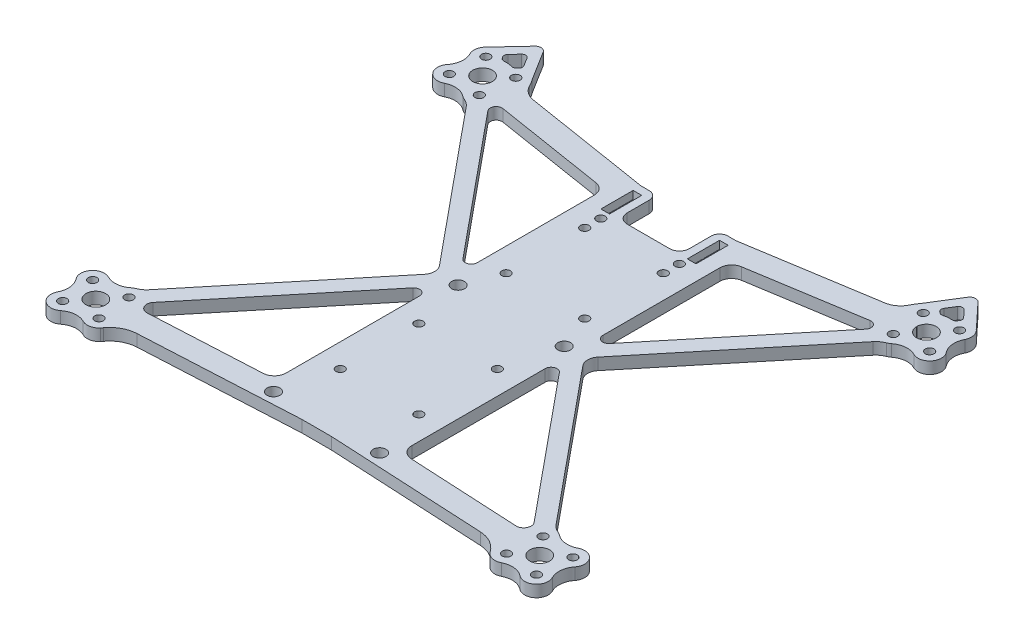
SolidWorks part; units mm, degrees
ref_plane "Front Plane" through (0, 0, 0) normal (0, 0, 1) x (1, 0, 0)
ref_plane "Top Plane" through (0, 0, 0) normal (0, 1, 0) x (1, 0, 0)
ref_plane "Right Plane" through (0, 0, 0) normal (1, 0, 0) x (0, 0, -1)
sketch "Sketch1" plane through (0, 0, 0) normal (0, 1, 0) x (1, 0, 0)
  line L0 (0, 42.225) -> (0, -42.225) construction
  line L1 (16, 42.225) -> (-16, 42.225)
  line L2 (16, 42.225) -> (16, -42.225)
  line L3 (16, -42.225) -> (-16, -42.225)
  line L4 (-16, 42.225) -> (-16, -42.225)
  line L5 (16, 42.225) -> (-16, -42.225) construction
  line L6 (16, -42.225) -> (-16, 42.225) construction
  line L12 (-12.1, 50.425) -> (-12.1, 52.425) construction
  line L17 (-11, 52.425) -> (-11, 42.225) construction
  line L18 (-7.9, 42.225) -> (-14.1, 42.225)
  line L20 (-10, 36) -> (10, 36)
  line L21 (-10, 36) -> (-10, 16)
  line L22 (-10, 16) -> (10, 16)
  line L23 (10, 36) -> (10, 16)
  line L24 (-10, 36) -> (10, 16) construction
  line L25 (-10, 16) -> (10, 36) construction
  line L26 (-14.5, 10.775) -> (14.5, 10.775)
  line L27 (-14.5, 10.775) -> (-14.5, 41.225)
  line L28 (-14.5, 41.225) -> (14.5, 41.225)
  line L29 (14.5, 10.775) -> (14.5, 41.225)
  line L30 (-14.5, 10.775) -> (14.5, 41.225) construction
  line L31 (-14.5, 41.225) -> (14.5, 10.775) construction
  line L32 (-10, -6.225) -> (10, -6.225)
  line L33 (-10, -6.225) -> (-10, -26.225)
  line L34 (-10, -26.225) -> (10, -26.225)
  line L35 (10, -6.225) -> (10, -26.225)
  line L36 (-10, -6.225) -> (10, -26.225) construction
  line L37 (-10, -26.225) -> (10, -6.225) construction
  line L38 (-15.75, -36.225) -> (15.75, -36.225)
  line L39 (-15.75, -36.225) -> (-15.75, 3.775)
  line L40 (-15.75, 3.775) -> (15.75, 3.775)
  line L41 (15.75, -36.225) -> (15.75, 3.775)
  line L42 (-15.75, -36.225) -> (15.75, 3.775) construction
  line L43 (-15.75, 3.775) -> (15.75, -36.225) construction
  line L48 (-7.9, 42.225) -> (-7.9, 52.425)
  line L49 (-7.9, 52.425) -> (-14.1, 52.425)
  line L59 (-14.1, 42.225) -> (-14.1, 52.425)
  line L63 (-12.1, 50.425) -> (-9.9, 50.425)
  line L64 (-12.1, 50.425) -> (-12.1, 42.225)
  line L65 (-12.1, 42.225) -> (-9.9, 42.225)
  line L66 (-9.9, 50.425) -> (-9.9, 42.225)
  line L67 (-12.1, 50.425) -> (-9.9, 42.225) construction
  line L68 (-12.1, 42.225) -> (-9.9, 50.425) construction
  line L69 (-12.1, 50.425) -> (-14.1, 50.425) construction
  line L74 (7.9, 42.225) -> (14.1, 42.225)
  line L75 (14.1, 42.225) -> (14.1, 52.425)
  line L76 (7.9, 52.425) -> (14.1, 52.425)
  line L77 (7.9, 42.225) -> (7.9, 52.425)
  line L78 (12.1, 50.425) -> (9.9, 50.425)
  line L79 (12.1, 50.425) -> (12.1, 42.225)
  line L80 (12.1, 42.225) -> (9.9, 42.225)
  line L81 (9.9, 50.425) -> (9.9, 42.225)
  line L82 (-14.5, 10.775) -> (-14.5, 3.775) construction
  line L83 (-14.5, 7.275) -> (16, 7.275) construction
  line L89 (-13.5, -37.225) -> (-16, -37.225) construction
  line L94 (-14.1, 52.425) -> (-16, 52.425)
  line L95 (-14.1, 52.425) -> (-14.1, 42.225)
  line L96 (-14.1, 42.225) -> (-16, 42.225)
  line L97 (-16, 52.425) -> (-16, 42.225)
  line L98 (14.1, 52.425) -> (16, 52.425)
  line L99 (14.1, 52.425) -> (14.1, 42.225)
  line L100 (14.1, 42.225) -> (16, 42.225)
  line L101 (16, 52.425) -> (16, 42.225)
  circle A3 centre (-10, 36) radius 1.1
  circle A4 centre (10, 36) radius 1.1
  circle A5 centre (10, 16) radius 1.1
  circle A6 centre (-10, 16) radius 1.1
  circle A7 centre (-10, -6.225) radius 1.1
  circle A8 centre (10, -6.225) radius 1.1
  circle A9 centre (10, -26.225) radius 1.1
  circle A10 centre (-10, -26.225) radius 1.1
  circle A37 centre (-13.5, 7.275) radius 2.5
  circle A38 centre (-13.5, 7.275) radius 1.625
  circle A39 centre (13.5, 7.275) radius 1.625
  circle A40 centre (-13.5, -39.725) radius 2.5
  circle A41 centre (-13.5, -39.725) radius 1.625
  circle A42 centre (13.5, -39.725) radius 1.625
  point P0 (0, 0)
  point P8 (0, 0)
  point P16 (0, 26)
  point P26 (0, 26)
  point P31 (0, -16.225)
  point P36 (0, -16.225)
  point P61 (-11, 46.325)
  dimension "D3" = 2
  dimension "D17" = 2.2
  dimension "D22" = 5
  dimension "D23" = 3.25
  dimension "D8" = 32
  dimension "D9" = 22
  dimension "D10" = 20
  dimension "D11" = 29
  dimension "D12" = 30.45
  dimension "D13" = 40
  dimension "D14" = 31.5
  dimension "D15" = 1
  dimension "D16" = 7
  dimension "D18" = 2.2
  dimension "D20" = 8.2
  dimension "D24" = 1
extrude "Base shape" add sketch "Sketch1" along normal blind 2 contours L63 L66 L1 L48 L49 L59 L18 L64 | L81 L78 L79 L1 L75 L76 L77 | L94 L97 L1 L59 | L101 L98 L75 L1 | L1 L4 L3 L2 | A4 | A3 | A7 | A8 | A9 | A10 | A5 | A6 | A39 | A38 | A41 | A42 region at (15.05, 0, -47.325) region at (13.1, 0, -42.3444) region at (-8.9, 0, -42.3444) region at (-15.05, 0, -47.325)
sketch "Sketch2" plane through (0, 0, 0) normal (0, -1, 0) x (1, 0, 0)
  line L0 (-12.1, -42.225) -> (-9.9, -50.425) construction
  line L1 (12.1, -42.225) -> (9.9, -50.425) construction
  line L4 (12.1, -42.225) -> (9.9, -42.225)
  line L5 (12.1, -50.425) -> (12.1, -42.225)
  line L6 (9.9, -50.425) -> (12.1, -50.425)
  line L7 (9.9, -42.225) -> (9.9, -50.425)
  line L8 (12.1, -42.225) -> (9.9, -42.225)
  line L9 (12.1, -50.425) -> (12.1, -42.225)
  line L10 (9.9, -50.425) -> (12.1, -50.425)
  line L11 (9.9, -42.225) -> (9.9, -50.425)
  line L12 (-9.9, -42.225) -> (-12.1, -42.225)
  line L13 (-9.9, -50.425) -> (-9.9, -42.225)
  line L14 (-12.1, -50.425) -> (-9.9, -50.425)
  line L15 (-12.1, -42.225) -> (-12.1, -50.425)
  line L16 (-9.9, -42.225) -> (-12.1, -42.225)
  line L17 (-9.9, -50.425) -> (-9.9, -42.225)
  line L18 (-12.1, -50.425) -> (-9.9, -50.425)
  line L19 (-12.1, -42.225) -> (-12.1, -50.425)
  circle A0 centre (-11, -46.325) radius 1.1
  circle A1 centre (11, -46.325) radius 1.1
  dimension "D1" = 0
  dimension "D2" = 0
extrude "Camera mount pockets" add sketch "Sketch2" against normal offset from surface (1 mm away) 1 contours A0 L19 | A0 L17 | A1 L9 | A1 L11 region at (11, 0, -43.8523) region at (11, 0, -48.7977) region at (-11, 0, -43.8523) region at (-11, 0, -48.7977) up to face at (11, 2, -46.325)
fillet "Main fillets" radius 2.5 6 edges at (7.9, 1, -42.225) (-7.9, 1, -42.225) (-16, 1, -52.425) (16, 1, -52.425) (-16, 1, 42.225) (16, 1, 42.225)
fillet "Inner camera mount fillets" radius 2.1 2 edges at (-7.9, 1, -52.425) (7.9, 1, -52.425)
sketch "Sketch3" plane through (0, 2, 0) normal (0, 1, 0) x (1, 0, 0)
  line L6 (12.1, 42.225) -> (12.1, 50.425)
  line L7 (9.9, 42.225) -> (12.1, 42.225)
  line L8 (-10, 52.425) -> (-13.5, 52.425)
  line L9 (-16, 49.925) -> (-16, -39.725)
  line L10 (-13.5, -42.225) -> (13.5, -42.225)
  line L11 (16, -39.725) -> (16, 49.925)
  line L12 (13.5, 52.425) -> (10, 52.425)
  line L13 (7.9, 50.325) -> (7.9, 44.725)
  line L14 (5.4, 42.225) -> (-5.4, 42.225)
  line L15 (-7.9, 44.725) -> (-7.9, 50.325)
  line L16 (-10, 52.425) -> (-13.5, 52.425)
  line L17 (-16, 49.925) -> (-16, -39.725)
  line L18 (-13.5, -42.225) -> (13.5, -42.225)
  line L19 (16, -39.725) -> (16, 49.925)
  line L20 (13.5, 52.425) -> (10, 52.425)
  line L21 (7.9, 50.325) -> (7.9, 44.725)
  line L22 (5.4, 42.225) -> (-5.4, 42.225)
  line L23 (-7.9, 44.725) -> (-7.9, 50.325)
  line L24 (9.9, 50.425) -> (9.9, 42.225)
  line L25 (12.1, 50.425) -> (9.9, 50.425)
  line L26 (12.1, 42.225) -> (12.1, 50.425)
  line L27 (9.9, 42.225) -> (12.1, 42.225)
  line L28 (9.9, 50.425) -> (9.9, 42.225)
  line L29 (12.1, 50.425) -> (9.9, 50.425)
  line L30 (-9.9, 42.225) -> (-9.9, 50.425)
  line L31 (-12.1, 42.225) -> (-9.9, 42.225)
  line L32 (-12.1, 50.425) -> (-12.1, 42.225)
  line L33 (-9.9, 50.425) -> (-12.1, 50.425)
  line L34 (-9.9, 42.225) -> (-9.9, 50.425)
  line L35 (-12.1, 42.225) -> (-9.9, 42.225)
  line L36 (-12.1, 50.425) -> (-12.1, 42.225)
  line L37 (-9.9, 50.425) -> (-12.1, 50.425)
  circle A0 centre (13.5, -39.725) radius 1.625 construction
  circle A1 centre (-13.5, -39.725) radius 1.625 construction
  circle A2 centre (-13.5, 7.275) radius 1.625 construction
  circle A3 centre (-10, -6.225) radius 1.1 construction
  circle A4 centre (-10, -26.225) radius 1.1 construction
  circle A5 centre (10, -26.225) radius 1.1 construction
  circle A6 centre (10, -6.225) radius 1.1 construction
  circle A7 centre (13.5, 7.275) radius 1.625 construction
  arc A8 (-13.5, 52.425) -> (-16, 49.925) centre (-13.5, 49.925) ccw
  arc A9 (-16, -39.725) -> (-13.5, -42.225) centre (-13.5, -39.725) ccw
  arc A10 (13.5, -42.225) -> (16, -39.725) centre (13.5, -39.725) ccw
  arc A11 (16, 49.925) -> (13.5, 52.425) centre (13.5, 49.925) ccw
  arc A12 (-7.9, 50.325) -> (-10, 52.425) centre (-10, 50.325) ccw
  arc A13 (5.4, 42.225) -> (7.9, 44.725) centre (5.4, 44.725) ccw
  arc A14 (-7.9, 44.725) -> (-5.4, 42.225) centre (-5.4, 44.725) ccw
  arc A15 (-7.9, 50.325) -> (-10, 52.425) centre (-10, 50.325) ccw
  arc A16 (-13.5, 52.425) -> (-16, 49.925) centre (-13.5, 49.925) ccw
  arc A17 (-16, -39.725) -> (-13.5, -42.225) centre (-13.5, -39.725) ccw
  arc A18 (13.5, -42.225) -> (16, -39.725) centre (13.5, -39.725) ccw
  arc A19 (16, 49.925) -> (13.5, 52.425) centre (13.5, 49.925) ccw
  arc A21 (5.4, 42.225) -> (7.9, 44.725) centre (5.4, 44.725) ccw
  arc A22 (-7.9, 44.725) -> (-5.4, 42.225) centre (-5.4, 44.725) ccw
  circle A24 centre (-10, 16) radius 1.1 construction
  circle A25 centre (-10, 36) radius 1.1 construction
  circle A26 centre (10, 36) radius 1.1 construction
  circle A27 centre (10, 16) radius 1.1 construction
  circle A28 centre (10, 16) radius 1.1
  circle A29 centre (10, 36) radius 1.1
  circle A30 centre (-10, 36) radius 1.1
  circle A31 centre (-10, 16) radius 1.1
  circle A32 centre (13.5, 7.275) radius 1.625
  circle A33 centre (10, -6.225) radius 1.1
  circle A34 centre (10, -26.225) radius 1.1
  circle A35 centre (-10, -26.225) radius 1.1
  circle A36 centre (-10, -6.225) radius 1.1
  circle A37 centre (13.5, -39.725) radius 1.625
  circle A38 centre (-13.5, -39.725) radius 1.625
  circle A39 centre (-13.5, 7.275) radius 1.625
  arc A48 (10, 52.425) -> (7.9, 50.325) centre (10, 50.325) ccw
  arc A49 (10, 52.425) -> (7.9, 50.325) centre (10, 50.325) ccw
  dimension "D1" = 0
  dimension "D2" = 0
  dimension "D3" = 0
extrude "Thicker base" add sketch "Sketch3" along normal blind 1
sketch "Sketch4" plane through (0, 0, 0) normal (0, -1, 0) x (1, 0, 0)
  line L0 (0, 13.9568) -> (0, -8.6953) construction
  line L1 (-13.1, -38.5) -> (-6.9, -38.5)
  line L2 (-14.1, -39.5) -> (-14.1, -40.7)
  line L3 (-13.1, -41.7) -> (-6.9, -41.7)
  line L4 (-5.9, -39.5) -> (-5.9, -40.7)
  line L5 (-10, -38.5) -> (-10, -41.7) construction
  line L7 (13.1, -38.5) -> (6.9, -38.5)
  line L8 (14.1, -39.5) -> (14.1, -40.7)
  line L9 (13.1, -41.7) -> (6.9, -41.7)
  line L10 (5.9, -39.5) -> (5.9, -40.7)
  line L12 (-14.1, -40.1) -> (-5.9, -40.1) construction
  circle A0 centre (-10, -36) radius 2
  arc A9 (14.1, -40.7) -> (13.1, -41.7) centre (13.1, -40.7) cw
  arc A10 (13.1, -38.5) -> (14.1, -39.5) centre (13.1, -39.5) cw
  arc A11 (6.9, -41.7) -> (5.9, -40.7) centre (6.9, -40.7) cw
  arc A12 (6.9, -38.5) -> (5.9, -39.5) centre (6.9, -39.5) ccw
  arc A13 (-6.9, -41.7) -> (-5.9, -40.7) centre (-6.9, -40.7) ccw
  arc A14 (-6.9, -38.5) -> (-5.9, -39.5) centre (-6.9, -39.5) cw
  arc A15 (-14.1, -40.7) -> (-13.1, -41.7) centre (-13.1, -40.7) ccw
  arc A16 (-13.1, -38.5) -> (-14.1, -39.5) centre (-13.1, -39.5) ccw
  point P9 (-10, -38)
  point P19 (14.1, -41.7)
  point P24 (14.1, -38.5)
  point P27 (5.9, -41.7)
  point P30 (5.9, -38.5)
  point P33 (-5.9, -41.7)
  point P36 (-5.9, -38.5)
  point P39 (-14.1, -41.7)
  point P42 (-14.1, -38.5)
  dimension "D5" = 4
  dimension "D6" = 1
  dimension "D1" = 8.2
  dimension "D2" = 3.2
  dimension "D3" = 10
  dimension "D4" = 0.5
extrude "Battery holder pockets" cut sketch "Sketch4" against normal blind 1 contours L4 L1 L2 L3 | L7 L10 L9 L8 region at (-10, 0, -40.1) region at (10, 0, -40.1)
sketch "Sketch5" plane through (0, 1, 0) normal (0, -1, 0) x (1, 0, 0)
  line L0 (-10, -38.5) -> (-10, -41.7) construction
  line L2 (-13.1, -41.7) -> (-6.9, -41.7) construction
  line L3 (0, 5.9884) -> (0, -5.6723) construction
  line L4 (-13.1, -38.5) -> (-6.9, -38.5) construction
  circle A0 centre (-10, -40.1) radius 1.1
  circle A1 centre (10, -40.1) radius 1.1
  point P2 (-10, -38.5)
  dimension "D1" = 2.2
extrude "Battery holder holes" cut sketch "Sketch5" against normal up to next
sketch "Sketch6" [suppressed] plane through (0, 0, 0) normal (0, -1, 0) x (1, 0, 0)
  line L0 (0, -5.1) -> (0, 9.653) construction
  line L8 (-13.5, -7.275) -> (13.5, -7.275) construction
  line L10 (-16, -25.775) -> (16, -25.775) construction
  line L11 (-16, -49.925) -> (-16, 39.725) construction
  line L12 (16, -49.925) -> (16, 39.725) construction
  line L13 (17.5, -34.275) -> (19, -34.275)
  line L14 (16, -37.275) -> (19, -37.275)
  line L15 (16, -37.275) -> (16, -14.275)
  line L16 (16, -14.275) -> (19, -14.275)
  line L17 (19, -37.275) -> (19, -14.275)
  line L18 (16, -37.275) -> (19, -14.275) construction
  line L19 (16, -14.275) -> (19, -37.275) construction
  line L20 (16, -35.775) -> (17.5, -35.775)
  line L21 (16, -35.775) -> (16, -15.775)
  line L22 (16, -15.775) -> (17.5, -15.775)
  line L23 (17.5, -35.775) -> (17.5, -15.775)
  line L24 (16, -35.775) -> (17.5, -15.775) construction
  line L25 (16, -15.775) -> (17.5, -35.775) construction
  line L26 (17.5, -17.275) -> (19, -17.275)
  line L27 (-17.5, -34.275) -> (-19, -34.275)
  line L28 (-17.5, -17.275) -> (-19, -17.275)
  line L29 (-16, -35.775) -> (-16, -15.775)
  line L30 (-16, -35.775) -> (-17.5, -35.775)
  line L31 (-17.5, -35.775) -> (-17.5, -15.775)
  line L32 (-16, -15.775) -> (-17.5, -15.775)
  line L33 (-16, -37.275) -> (-16, -14.275)
  line L34 (-16, -37.275) -> (-19, -37.275)
  line L35 (-19, -37.275) -> (-19, -14.275)
  line L36 (-16, -14.275) -> (-19, -14.275)
  line L37 (16, 22.725) -> (19, 22.725)
  line L38 (16, 22.725) -> (16, -0.275)
  line L39 (16, -0.275) -> (19, -0.275)
  line L40 (19, 22.725) -> (19, -0.275)
  line L41 (16, 21.225) -> (17.5, 21.225)
  line L42 (16, 21.225) -> (16, 1.225)
  line L43 (16, 1.225) -> (17.5, 1.225)
  line L44 (17.5, 21.225) -> (17.5, 1.225)
  line L45 (17.5, 2.725) -> (19, 2.725)
  line L46 (17.5, 19.725) -> (19, 19.725)
  line L47 (-17.5, 19.725) -> (-19, 19.725)
  line L48 (-17.5, 2.725) -> (-19, 2.725)
  line L49 (-16, 21.225) -> (-16, 1.225)
  line L50 (-16, 21.225) -> (-17.5, 21.225)
  line L51 (-17.5, 21.225) -> (-17.5, 1.225)
  line L52 (-16, 1.225) -> (-17.5, 1.225)
  line L53 (-16, 22.725) -> (-16, -0.275)
  line L54 (-16, 22.725) -> (-19, 22.725)
  line L55 (-19, 22.725) -> (-19, -0.275)
  line L56 (-16, -0.275) -> (-19, -0.275)
  point P19 (17.5, -25.775)
  point P25 (16.75, -25.775)
  line M18 (16, -49.925) -> (16, 39.725)
  line M22 (-16, 39.725) -> (-16, -49.925)
  dimension "D1" = 14
  dimension "D4" = 23
  dimension "D5" = 3
  dimension "D6" = 1.5
  dimension "D7" = 20
  dimension "D8" = 1.5
extrude "Strap holders" [suppressed] add sketch "Sketch6" against normal up to surface (2 mm away) contours L23 L20 L14 L17 L13 M18 | L23 L26 L17 L16 L22 M18 | L45 L44 L43 L39 L40 M18 | L44 L46 L40 L37 L38 L41 | L54 L55 L47 L51 L50 M22 | L56 L52 L51 L48 L55 M22 | L36 L35 L28 L31 L32 M22 | L35 L34 L30 L31 L27 M22 up to face at (-10, 3, -39)
fillet "Strap holder fillets" [suppressed] radius 0.75
sketch "Sketch7" plane through (0, 3, 0) normal (0, 1, 0) x (1, 0, 0)
  line L0 (-56.5, 56.5) -> (-16, 50.0116) construction
  line L1 (56.5, -56.5) -> (-56.5, -56.5)
  line L2 (56.5, -56.5) -> (56.5, 56.5)
  line L3 (56.5, 56.5) -> (-56.5, 56.5)
  line L4 (-56.5, -56.5) -> (-56.5, 56.5)
  line L5 (56.5, -56.5) -> (-56.5, 56.5) construction
  line L6 (56.5, 56.5) -> (-56.5, -56.5) construction
  line L7 (-16, 49.925) -> (-16, -39.725) construction
  line L8 (-56.9746, 53.5378) -> (-16.4746, 47.0493)
  line L9 (-47.647, 58.1199) -> (-12.1, 52.425)
  line L10 (-56.0254, 59.4622) -> (-15.5254, 52.9738) construction
  line L11 (-13.5, 7.275) -> (13.5, 7.275) construction
  line L12 (-63.45, 50.7819) -> (-49.55, 62.2181) construction
  line L13 (-56.5, 56.5) -> (-16, 7.275) construction
  line L14 (-58.0444, 55.2293) -> (-17.5444, 6.0043)
  line L15 (-54.9556, 57.7707) -> (-14.4556, 8.5457)
  line L16 (-17.5444, 6.0043) -> (-16, 4.1271)
  line L17 (-56.5, 56.5) -> (-60.3121, 61.1333) construction
  line L18 (-56.5, 65.5) -> (-56.5, 47.5) construction
  line L19 (-60.3121, 61.1333) -> (-51.8667, 60.3121) construction
  line L20 (-56.0894, 60.7227) -> (-55.3151, 68.6852) construction
  line L21 (-56.4116, 69.7087) -> (-62.3842, 63.31)
  line L22 (-54.0419, 69.4782) -> (-49.414, 62.0488)
  line L23 (-55.4603, 67.1922) -> (-58.7341, 63.6848)
  line L24 (-55.4603, 67.1922) -> (-52.9235, 63.1198)
  line L25 (-58.0444, -40.6793) -> (-17.5444, 8.5457)
  line L26 (-54.9556, -43.2207) -> (-14.4556, 6.0043)
  line L27 (-56.5, -41.95) -> (-13.5, -39.725) construction
  line L28 (-47.871, -44.5075) -> (-3.7595, -42.225)
  line L29 (-56.655, -38.954) -> (-16, -36.8503)
  line L30 (-56.345, -44.946) -> (-14.5762, -42.7847) construction
  line L31 (-56.5, -41.95) -> (-14.7312, -39.7887) construction
  line L32 (-13.5, -42.225) -> (13.5, -42.225) construction
  line L33 (-56.655, -38.954) -> (-14.8862, -36.7927) construction
  line L34 (-16.4746, 47.0493) -> (-16, 46.9733)
  line L35 (-12.1, 50.425) -> (-12.1, 52.425) construction
  line L36 (-10, 52.425) -> (-13.5, 52.425) construction
  circle A0 centre (-56.5, 56.5) radius 38.1
  circle A1 centre (-56.5, 56.5) radius 9
  circle A2 centre (-56.5, 56.5) radius 6
  circle A3 centre (-51.8667, 60.3121) radius 1.1
  circle A4 centre (-61.1333, 52.6879) radius 1.1
  circle A5 centre (-60.3121, 61.1333) radius 1.1
  circle A6 centre (-52.6879, 51.8667) radius 1.1
  circle A7 centre (-60.3121, 61.1333) radius 3
  circle A8 centre (-51.8667, 60.3121) radius 3
  circle A9 centre (-61.1333, 52.6879) radius 3
  circle A10 centre (-52.6879, 51.8667) radius 3
  circle A12 centre (-56.5, 56.5) radius 2.5
  circle A13 centre (-55.3151, 68.6852) radius 1.5
  circle A14 centre (-67.313, 57.5515) radius 4.864
  circle A15 centre (-57.5515, 45.687) radius 4.864
  circle A16 centre (-43.9819, 62.4587) radius 4.864
  circle A17 centre (-55.5501, 44.5421) radius 4.864
  circle A18 centre (-46.9606, 50.4143) radius 1.5
  circle A20 centre (-56.5, -41.95) radius 6
  circle A21 centre (-52.6879, -37.3167) radius 1.1
  circle A22 centre (-61.1333, -38.1379) radius 1.1
  circle A23 centre (-60.3121, -46.5833) radius 1.1
  circle A24 centre (-51.8667, -45.7621) radius 1.1
  circle A25 centre (-51.8667, -45.7621) radius 3
  circle A26 centre (-52.6879, -37.3167) radius 3
  circle A27 centre (-56.5, -41.95) radius 2.5
  circle A28 centre (-60.3121, -46.5833) radius 3
  circle A29 centre (-67.313, -43.0015) radius 4.864
  circle A30 centre (-61.1333, -38.1379) radius 3
  circle A31 centre (-57.5515, -31.137) radius 4.864
  circle A32 centre (-55.5501, -29.9921) radius 4.864
  circle A34 centre (-56.5, -41.95) radius 9
  circle A35 centre (-55.4485, -52.763) radius 4.864
  circle A38 centre (-43.36, -51.5674) radius 7.2836
  circle A39 centre (-47.0369, -36.5665) radius 1.8873
  point P0 (0, 0)
  point P36 (-52.6879, 51.8667)
  point P54 (-55.4603, 67.1922)
  arc M21 (-7.9, 50.325) -> (-10, 52.425) centre (-10, 50.325) ccw
  line M22 (-10, 52.425) -> (-13.5, 52.425)
  arc M23 (-13.5, 52.425) -> (-16, 49.925) centre (-13.5, 49.925) ccw
  line M24 (-16, 49.925) -> (-16, -39.725)
  arc M25 (-16, -39.725) -> (-13.5, -42.225) centre (-13.5, -39.725) ccw
  line M26 (-13.5, -42.225) -> (13.5, -42.225)
  dimension "D3" = 76.2
  dimension "D4" = 12
  dimension "D5" = 3
  dimension "D10" = 2.2
  dimension "D11" = 5
  dimension "D12" = 3
  dimension "D16" = 3
  dimension "D1" = 113
  dimension "D13" = 8
  dimension "D6" = 3
  dimension "D7" = 3
  dimension "D8" = 2
  dimension "D9" = 2
  dimension "D14" = 3
  dimension "D15" = 3
extrude "Arms" add sketch "Sketch7" against normal up to surface (3 mm away) contours A0 L8 L34 L9 M24 M23 M22 M21 | A1 L8 A0 L9 L3 | A10 L8 A1 L3 A2 | A16 L3 L9 | A8 A2 L3 A1 | A2 A8 A3 | A2 A8 A3 | A12 L3 A2 A8 A7 A9 L4 L14 | A12 L15 A10 A2 L3 | A12 L4 L8 A10 L15 | A12 L14 L8 L4 | A10 L8 L4 L14 | A10 L14 L4 A2 | L8 L14 L4 | A14 A9 A2 | A14 A2 A7 | A15 A2 A9 | A15 A10 A2 L4 | A10 L15 A1 L8 | A10 A1 L15 | A17 A1 L14 A10 | A10 L14 A1 | A17 L14 A1 | A1 L14 A0 L15 | A8 A1 L24 | A13 L24 A1 L22 | A13 | A13 L21 A1 L23 | A7 L23 A1 | A0 L14 L16 L15 M24 | L25 A34 L26 L16 L14 | L29 A34 L28 M26 M25 M24 | A39 L26 A34 | A39 A34 L29 | A34 L25 A26 | A34 A32 A26 L25 | A32 A34 L25 | A26 A31 L4 A20 | L4 A31 A20 | L25 A26 A20 L4 | A20 A30 A28 L4 A27 L25 | A20 A31 A30 | A20 A30 A29 | A20 A29 A28 | A35 L4 A20 A28 | A35 A25 A20 | L26 A27 L4 A20 A25 A26 | A35 A20 L4 | L4 A27 L26 A26 L29 | L29 A26 L25 L4 | L25 L29 L4 | L25 A27 L4 L29 | A38 L28 A34 | A34 L29 A26 A20 A25 | A34 L26 A26 L29 | A34 A26 L26 | A15 L4 A2 | A18 L8 A1 L15 | A1 L3 L9 | A7 | A5 | A9 | A4 | A10 | A6 | A26 | A21 | A30 | A22 | A28 | A23 | A25 | A24 region at (-47.184, 3, 45.066) region at (-31.3338, 3, 40.711) region at (-32.8289, 3, -52.5874) region at (-44.211, 3, -57.0386) region at (-17.1717, 3, -50.3538) region at (-48.9969, 3, 41.7471) region at (-49.1236, 3, -54.6581) region at (-48.8324, 3, -58.0351) region at (-47.1282, 3, -58.5028) region at (-24.1765, 3, -17.1136) region at (-41.5668, 3, -38.3497) region at (-57.4052, 3, 48.163) region at (-54.4445, 3, 47.8724) region at (-51.8807, 3, -55.6768) region at (-52.205, 3, -56.6697) region at (-49.2822, 3, -51.8002) region at (-48.4949, 3, -51.2849) region at (-52.3363, 3, -48.2332) region at (-34.0657, 3, 14.6748) region at (-56.355, 3, 47.9664) region at (-62.4224, 3, 44.0055) region at (-57.252, 3, 47.2609) region at (-55.1154, 3, 47.6835) region at (-48.0098, 3, 38.2823) region at (-49.1686, 3, 37.7777) region at (-54.4837, 3, -54.6883) region at (-53.0659, 3, -59.3254) region at (-50.9193, 3, -61.0916) region at (-49.7951, 3, -50.7418) region at (-52.9788, 3, -65.9755) region at (-52.3363, 3, 33.6832) region at (-52.9015, 3, -48.7171) region at (-52.1414, 3, -48.8113) region at (-49.026, 3, 36.4293) region at (-55.3151, 3, -68.6852) region at (-52.4447, 3, -63.9477) region at (-52.1414, 3, 34.2613) region at (-52.9015, 3, 34.1671) region at (-58.5555, 3, 36.0276) region at (-58.5555, 3, -50.5776) region at (-62.7075, 3, 41.0741) region at (-49.7951, 3, 36.1918) region at (-56.6984, 3, -53.811) region at (-55.8748, 3, -53.0321) region at (-58.1296, 3, -66.4764) region at (-55.5948, 3, 35.737) region at (-56.645, 3, 35.9336) region at (-56.645, 3, -50.4836) region at (-55.5948, 3, -50.287) region at (-62.7075, 3, -55.6241) region at (-56.701, 3, 39.2669) region at (-54.4356, 3, 40.1886) region at (-56.5346, 3, -53.4308) region at (-56.0913, 3, -51.6584) region at (-59.0444, 3, -64.5895) region at (-56.0913, 3, 37.1084) region at (-62.4224, 3, -58.5555) region at (-56.5412, 3, 38.9002) region at (-55.8564, 3, 38.5438) up to face at (-13.5, 0, 41.35)
fillet "Motor protector fillets" radius 1 5 edges at (-52.9235, 1.5, -63.1198) (-54.2913, 1.5, -62.0787) (-57.5925, 1.5, -62.3997) (-58.7341, 1.5, -63.6848) (-55.4603, 1.5, -67.1922)
mirror "Arms mirror" about plane through (0, 0, 0) normal (1, 0, 0) of "Arms", "Motor protector fillets"
fillet "Arm fillets outer" radius 3 6 edges at (-16, 1.5, 36.8503) (-16, 1.5, -46.9733) (-18.5899, 1.5, -7.275) (16, 1.5, 36.8503) (18.5899, 1.5, -7.275) (16, 1.5, -46.9733)
fillet "Arm fillets inner" radius 1.5 4 edges at (-16, 1.5, -10.4229) (-16, 1.5, -4.1271) (16, 1.5, -4.1271) (16, 1.5, -10.4229)
